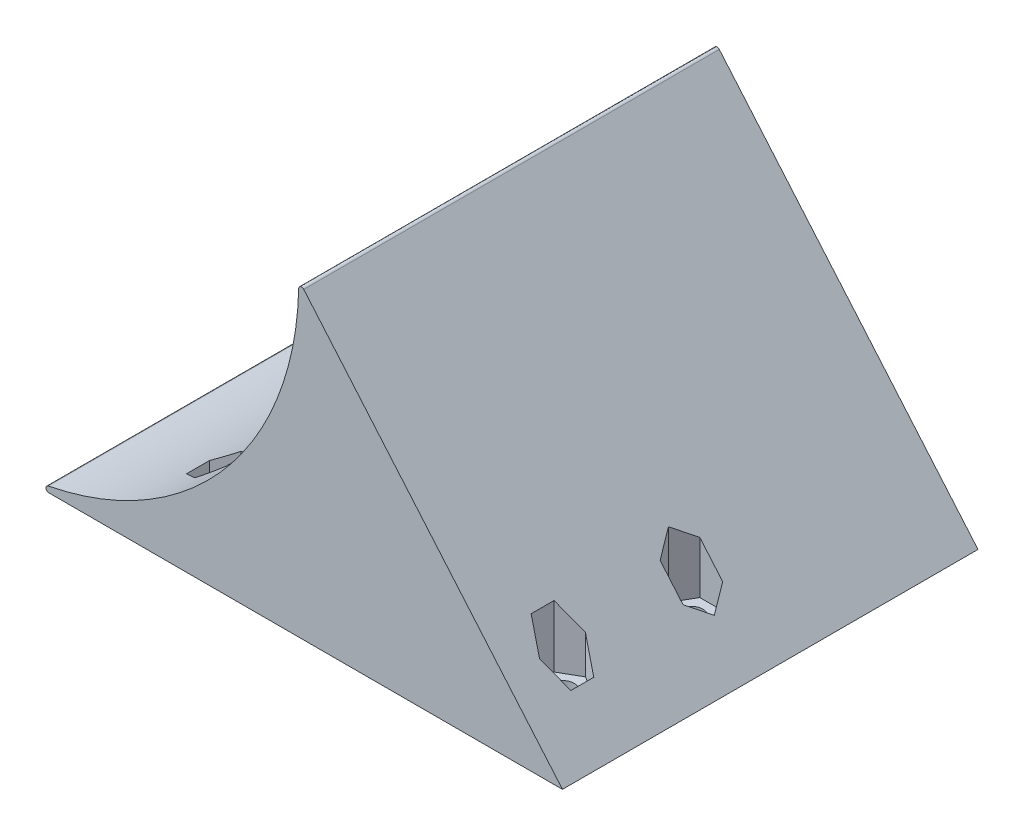
SolidWorks part; units mm, degrees
ref_plane "前视基准面" through (0, 0, 0) normal (0, 0, 1) x (1, 0, 0)
ref_plane "上视基准面" through (0, 0, 0) normal (0, 1, 0) x (1, 0, 0)
ref_plane "右视基准面" through (0, 0, 0) normal (1, 0, 0) x (0, 0, -1)
sketch "草图2" plane through (0, 0, 0) normal (0, 0, 1) x (1, 0, 0)
  circle A1 centre (0, 0) radius 33.5
  dimension "D3" = 67
sketch "草图3" plane through (0, 0, 0) normal (0, 0, 1) x (1, 0, 0)
  line L0 (0, 0) -> (0, -54) construction
  line L1 (0, -54) -> (100, -54) construction
  line L2 (100, -54) -> (0, -54)
  line L3 (54, 0) -> (100, -54)
  circle A1 centre (0, 0) radius 33.5 construction
  circle A2 centre (0, 0) radius 35.5
  arc A3 (0, -54) -> (54, 0) centre (0, 0) ccw
  dimension "D3" = 2
  dimension "D4" = 54
  dimension "D1" = 54
  dimension "D2" = 100
extrude "凸台-拉伸1" add sketch "草图3" along normal mid plane 145 contours A3 L2 A2 region at (60.1549, -37.9895, 0)
fillet "圆角1" radius 0.5 2 edges at (0, -54, 0) (54, 0, 0)
sketch "草图4" plane through (0, 0, 0) normal (0, 1, 0) x (1, 0, 0)
  line L1 (93.4641, -64.5) -> (93.4641, -60.5)
  line L2 (93.4641, -60.5) -> (90, -58.5)
  line L3 (90, -58.5) -> (86.5359, -60.5)
  line L4 (86.5359, -60.5) -> (86.5359, -64.5)
  line L5 (86.5359, -64.5) -> (90, -66.5)
  line L6 (90, -66.5) -> (93.4641, -64.5)
  line L7 (29.8923, -58.5) -> (26.4282, -60.5)
  line L8 (26.4282, -60.5) -> (26.4282, -64.5)
  line L9 (26.4282, -64.5) -> (29.8923, -66.5)
  line L10 (29.8923, -66.5) -> (33.3564, -64.5)
  line L11 (33.3564, -64.5) -> (33.3564, -60.5)
  line L12 (33.3564, -60.5) -> (29.8923, -58.5)
  line L14 (10.297, -72.5) -> (53.9837, -72.5) construction
  line L15 (90, -62.5) -> (90, 62.5) construction
  line L16 (9.8923, 72.5) -> (9.8923, -72.5) construction
  line L17 (0, 0) -> (131, 0) construction
  line L18 (-33.5, 0) -> (33.5, 0) construction
  line L19 (33.3564, 60.5) -> (29.8923, 58.5)
  line L20 (33.3564, 64.5) -> (33.3564, 60.5)
  line L21 (29.8923, 66.5) -> (33.3564, 64.5)
  line L22 (26.4282, 64.5) -> (29.8923, 66.5)
  line L23 (26.4282, 60.5) -> (26.4282, 64.5)
  line L24 (29.8923, 58.5) -> (26.4282, 60.5)
  line L25 (90, 66.5) -> (93.4641, 64.5)
  line L26 (86.5359, 64.5) -> (90, 66.5)
  line L27 (86.5359, 60.5) -> (86.5359, 64.5)
  line L28 (90, 58.5) -> (86.5359, 60.5)
  line L29 (93.4641, 60.5) -> (90, 58.5)
  line L30 (93.4641, 64.5) -> (93.4641, 60.5)
  line L31 (29.8923, -62.5) -> (90, -62.5) construction
  line L32 (92, -36.5359) -> (88, -36.5359)
  line L33 (88, -36.5359) -> (86, -40)
  line L34 (86, -40) -> (88, -43.4641)
  line L35 (88, -43.4641) -> (92, -43.4641)
  line L36 (92, -43.4641) -> (94, -40)
  line L37 (94, -40) -> (92, -36.5359)
  line L38 (94, 40) -> (92, 43.4641)
  line L39 (92, 43.4641) -> (88, 43.4641)
  line L40 (88, 43.4641) -> (86, 40)
  line L41 (86, 40) -> (88, 36.5359)
  line L42 (88, 36.5359) -> (92, 36.5359)
  line L43 (92, 36.5359) -> (94, 40)
  line L44 (90, -62.5) -> (93.4641, -114.585) construction
  line L45 (100, -72.5) -> (100, 72.5) construction
  circle A0 centre (90, -62.5) radius 3.4641 construction
  circle A1 centre (29.8923, -62.5) radius 3.4641 construction
  circle A2 centre (29.8923, 62.5) radius 3.4641 construction
  circle A3 centre (90, 62.5) radius 3.4641 construction
  circle A4 centre (90, -40) radius 3.4641 construction
  circle A5 centre (90, 40) radius 3.4641 construction
  dimension "D1" = 4
  dimension "D2" = 10
  dimension "D4" = 10
  dimension "D5" = 20
  dimension "D6" = 80
extrude "切除-拉伸1" cut sketch "草图4" against normal offset from surface (49 mm away) 5 up to face at (55.1962, -54, 0)
sketch "草图5" plane through (0, -49, 0) normal (0, 1, 0) x (1, 0, 0)
  line L0 (33.0636, -110) -> (26.1354, -110) construction
  line L1 (90, -62.5) -> (90, 62.5) construction
  line L3 (31.6244, -59.5) -> (28.1603, -65.5) construction
  line L6 (33.3564, -60.5) -> (29.8923, -58.5) construction
  line L7 (29.8923, -66.5) -> (26.4282, -64.5) construction
  line L8 (26.1354, -110) -> (33.0636, -110) construction
  line L10 (59.9462, 0) -> (0, 0) construction
  line L14 (59.9462, -110) -> (33.0636, -110) construction
  line L17 (59.9462, -110) -> (59.9462, 110) construction
  line L18 (26.4282, 62.5) -> (93.4641, 62.5) construction
  line L21 (-33.5, 0) -> (33.5, 0) construction
  line L22 (26.4282, 64.5) -> (26.4282, 60.5) construction
  line L25 (87, 38.2679) -> (93, 41.7321) construction
  line L27 (94, 40) -> (92, 43.4641) construction
  line L32 (86, 40) -> (88, 36.5359) construction
  circle A0 centre (29.8923, -62.5) radius 2.05
  circle A2 centre (29.8923, 62.5) radius 2.05
  circle A6 centre (90, 62.5) radius 2.05
  circle A7 centre (90, -62.5) radius 2.05
  circle A8 centre (90, 40) radius 2.05
  circle A9 centre (90, -40.0646) radius 2.05
  point P17 (59.9462, 62.5)
  point P49 (29.8923, -62.5)
  dimension "D1" = 4.1
extrude "切除-拉伸2" cut sketch "草图5" against normal blind 5 contours A0 | A8 | A2 | A7 | A9 | A6 region at (29.8923, -49, 62.5) region at (90, -49, -40)
sketch "草图6" plane through (0, 0, 0) normal (0, 0, 1) x (1, 0, 0)
  line L0 (100, -54) -> (10.3923, -54) construction
  circle A0 centre (51.8987, -54) radius 74.1946
extrude "切除-拉伸3" cut sketch "草图6" against normal through all
